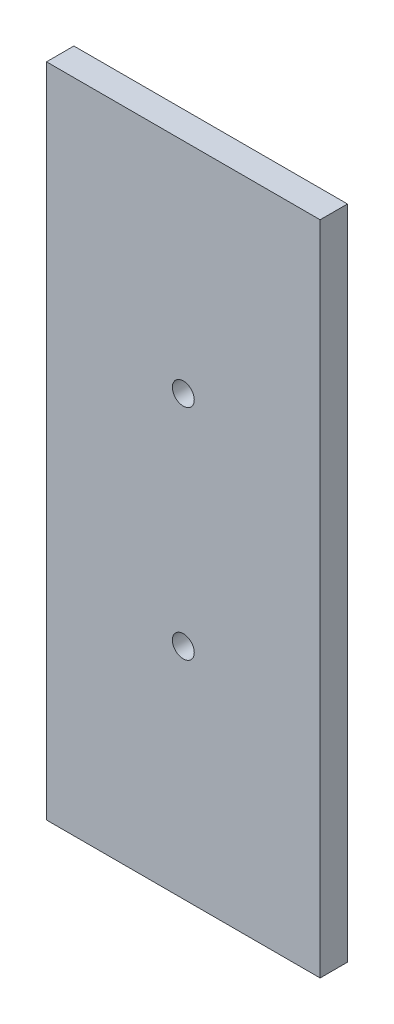
SolidWorks part; units mm, degrees
ref_plane "Plan de face" through (0, 0, 0) normal (0, 0, 1) x (1, 0, 0)
ref_plane "Plan de dessus" through (0, 0, 0) normal (0, 1, 0) x (1, 0, 0)
ref_plane "Plan de droite" through (0, 0, 0) normal (1, 0, 0) x (0, 0, -1)
sketch "Esquisse1" plane through (0, 0, 0) normal (0, 0, 1) x (1, 0, 0)
  line L0 (-25, 0) -> (25, 0) construction
  line L1 (-25, -60) -> (25, -60)
  line L2 (-25, -60) -> (-25, 60)
  line L3 (-25, 60) -> (25, 60)
  line L4 (25, -60) -> (25, 60)
  line L5 (-25, -60) -> (25, 60) construction
  line L6 (-25, 60) -> (25, -60) construction
  line L8 (0, 60) -> (0, -60) construction
  circle A0 centre (0, 20) radius 2
  circle A1 centre (0, -20) radius 2
  point P0 (0, 0)
  dimension "D3" = 4
  dimension "D4" = 4
  dimension "D5" = 20
  dimension "D1" = 120
  dimension "D2" = 50
  dimension "D6" = 20
extrude "Boss.-Extru.1" add sketch "Esquisse1" along normal blind 5
